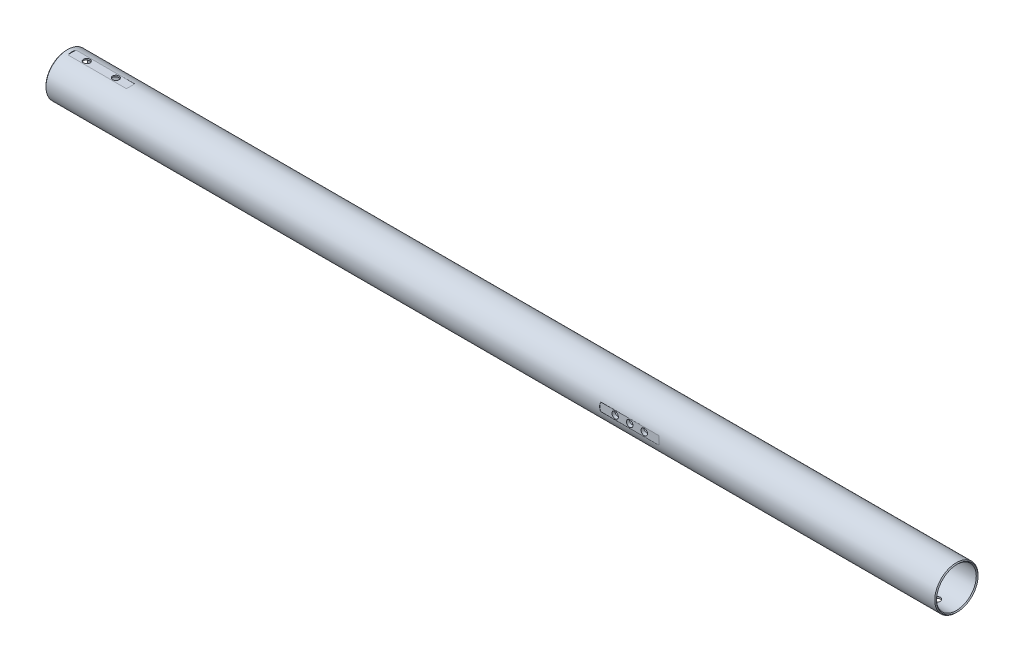
SolidWorks part; units mm, degrees
material "Stainless Steel (ferritic)"
ref_plane "Front Plane" through (0, 0, 0) normal (0, 0, 1) x (1, 0, 0)
ref_plane "Top Plane" through (0, 0, 0) normal (0, 1, 0) x (1, 0, 0)
ref_plane "Right Plane" through (0, 0, 0) normal (1, 0, 0) x (0, 0, -1)
sketch "Sketch1" plane through (0, 0, 0) normal (1, 0, 0) x (0, 0, -1)
  circle A0 centre (0, 0) radius 25
  dimension "D1" = 50
extrude "Extrude-Thin1" add sketch "Sketch1" along normal mid plane 1030 thin thin type one direction reverse wall 2
extrude "Extrude-Thin2" add sketch "Sketch1<3>" against normal blind 90 from offset 210 thin thin type one direction reverse wall 4
sketch "Sketch1<3>" plane through (0, 0, 0) normal (1, 0, 0) x (0, 0, -1) same geometry as "Sketch1"
sketch "Sketch3" plane through (0, 0, 0) normal (0, 1, 0) x (1, 0, 0)
  line L0 (-491.7775, 0) -> (-458.1225, 0) construction
  line L1 (-491.7775, 17.4725) -> (-458.1225, 17.4725)
  line L2 (-491.7775, -17.4725) -> (-458.1225, -17.4725)
  line L4 (-515, 25) -> (-515, -25) construction
  line L5 (0, -27.5) -> (0, 27.5) construction
  line L6 (491.7775, 0) -> (458.1225, 0) construction
  line L7 (491.7775, 17.4725) -> (458.1225, 17.4725)
  line L8 (491.7775, -17.4725) -> (458.1225, -17.4725)
  arc A1 (-491.7775, 17.4725) -> (-491.7775, -17.4725) centre (-491.7775, 0) ccw
  arc A2 (-458.1225, -17.4725) -> (-458.1225, 17.4725) centre (-458.1225, 0) ccw
  arc A3 (491.7775, 17.4725) -> (491.7775, -17.4725) centre (491.7775, 0) cw
  arc A4 (458.1225, -17.4725) -> (458.1225, 17.4725) centre (458.1225, 0) cw
  point P3 (-474.95, 0)
  point P14 (474.95, 0)
  point P19 (0, 0)
  dimension "D2" = 5.75
  dimension "D1" = 68.6
  dimension "D3" = 33.655
extrude "Cut-Extrude1" cut sketch "Sketch3" along normal through all from offset 24.54 contours L2 A2 L1 A1 region at (-474.95, 0, 0)
sketch "Sketch8" plane through (0, 0, 0) normal (0, 0, 1) x (1, 0, 0)
  line L0 (-272.5275, 0) -> (-238.8725, 0) construction
  line L1 (-272.5275, 17.4725) -> (-238.8725, 17.4725)
  line L2 (-272.5275, -17.4725) -> (-238.8725, -17.4725)
  line L4 (-515, 25) -> (-515, -25) construction
  line L5 (143.8725, 0) -> (177.5275, 0) construction
  line L6 (143.8725, 17.4725) -> (177.5275, 17.4725)
  line L7 (143.8725, -17.4725) -> (177.5275, -17.4725)
  line L13 (515, -25) -> (515, 25) construction
  arc A1 (-272.5275, 17.4725) -> (-272.5275, -17.4725) centre (-272.5275, 0) ccw
  arc A2 (-238.8725, -17.4725) -> (-238.8725, 17.4725) centre (-238.8725, 0) ccw
  arc A3 (143.8725, 17.4725) -> (143.8725, -17.4725) centre (143.8725, 0) ccw
  arc A4 (177.5275, -17.4725) -> (177.5275, 17.4725) centre (177.5275, 0) ccw
  point P0 (389.2317, 0)
  point P3 (-255.7, 0)
  point P13 (160.7, 0)
  dimension "D2" = 225
  dimension "D1" = 68.6
  dimension "D3" = 33.655
  dimension "D6" = 320
  dimension "D4" = 68.6
  dimension "D5" = 33.655
extrude "Cut-Extrude2" cut sketch "Sketch8" against normal through all from offset 24.54 contours L2 A2 L1 A1 region at (-255.7, 0, 0) offset against normal yes
extrude "Cut-Extrude3" cut sketch "Sketch3<3>" against normal through all from offset 24.54 contours A4 L8 A3 L7 region at (474.95, 0, 0) offset against normal yes
sketch "Sketch3<3>" plane through (0, 0, 0) normal (0, 1, 0) x (1, 0, 0) same geometry as "Sketch3"
extrude "Cut-Extrude4" cut sketch "Sketch8<4>" along normal through all from offset 24.54 contours L7 A4 L6 A3 region at (160.7, 0, 0)
sketch "Sketch8<4>" plane through (0, 0, 0) normal (0, 0, 1) x (1, 0, 0) same geometry as "Sketch8"
sketch "Sketch11" plane through (0, 24.54, 0) normal (0, 1, 0) x (1, 0, 0)
  point P0 (-491.7775, 0)
  point P3 (-458.1225, 0)
hole_wizard "M (0.295) Diameter Hole3" positions "Sketch11" profile "Sketch12" hole size "M" standard "ANSI Inch" end condition up to next
sketch "Sketch12" plane through (-491.7775, 24.54, 0) normal (1, 0, 0) x (0, 0, 1)
  line L0 (0, 0) -> (0, 1.54)
  line L1 (0, 1.54) -> (3.7465, 1.54)
  line L2 (3.7465, 1.54) -> (3.7465, 0)
  line L5 (3.7465, 0) -> (0, 0)
  line L11 (0, -6.35) -> (0, 107.95) construction
  dimension "Thru Hole Dia." = 7.493
  dimension "Thru Hole Depth" = 1.54
sketch "Sketch13" plane through (0, 0, -24.54) normal (0, 0, -1) x (-1, 0, 0)
  point P0 (238.8725, 0)
  point P3 (272.5275, 0)
hole_wizard "M (0.295) Diameter Hole4" positions "Sketch13" profile "Sketch14" hole size "M" standard "ANSI Inch" end condition up to next
sketch "Sketch14" plane through (-238.8725, 0, -24.54) normal (1, 0, 0) x (0, 1, 0)
  line L0 (0, 0) -> (0, 1.54)
  line L1 (0, 1.54) -> (3.7465, 1.54)
  line L2 (3.7465, 1.54) -> (3.7465, 0)
  line L5 (3.7465, 0) -> (0, 0)
  line L11 (0, -6.35) -> (0, 107.95) construction
  dimension "Thru Hole Dia." = 7.493
  dimension "Thru Hole Depth" = 1.54
hole_wizard "M (0.295) Diameter Hole5" positions "Sketch15" profile "Sketch16" hole size "M" standard "ANSI Inch" end condition up to next
sketch "Sketch15" plane through (0, 0, 24.54) normal (0, 0, 1) x (1, 0, 0)
  point P0 (143.8725, 0)
  point P3 (160.7, 0)
  point P6 (177.5275, 0)
sketch "Sketch16" plane through (143.8725, 0, 24.54) normal (1, 0, 0) x (0, -1, 0)
  line L0 (0, 0) -> (0, 3.54)
  line L1 (0, 3.54) -> (3.7465, 3.54)
  line L2 (3.7465, 3.54) -> (3.7465, 0)
  line L5 (3.7465, 0) -> (0, 0)
  line L11 (0, -6.35) -> (0, 107.95) construction
  dimension "Thru Hole Dia." = 7.493
  dimension "Thru Hole Depth" = 3.54
sketch "Sketch18" plane through (0, -24.54, 0) normal (0, -1, 0) x (-1, 0, 0)
  point P0 (-491.7775, 0)
  point P3 (-458.1225, 0)
hole_wizard "M (0.295) Diameter Hole6" positions "Sketch18" profile "Sketch19" hole size "M" standard "ANSI Inch" end condition up to next
sketch "Sketch19" plane through (491.7775, -24.54, 0) normal (1, 0, 0) x (0, 0, -1)
  line L0 (0, 0) -> (0, 1.54)
  line L1 (0, 1.54) -> (3.7465, 1.54)
  line L2 (3.7465, 1.54) -> (3.7465, 0)
  line L5 (3.7465, 0) -> (0, 0)
  line L11 (0, -6.35) -> (0, 107.95) construction
  dimension "Thru Hole Dia." = 7.493
  dimension "Thru Hole Depth" = 1.54
chamfer "Chamfer1" distance 1 angle 45 4 edges at (-515, 0, -23) (-515, 0, -25) (515, 0, -23) (515, 0, -25)
